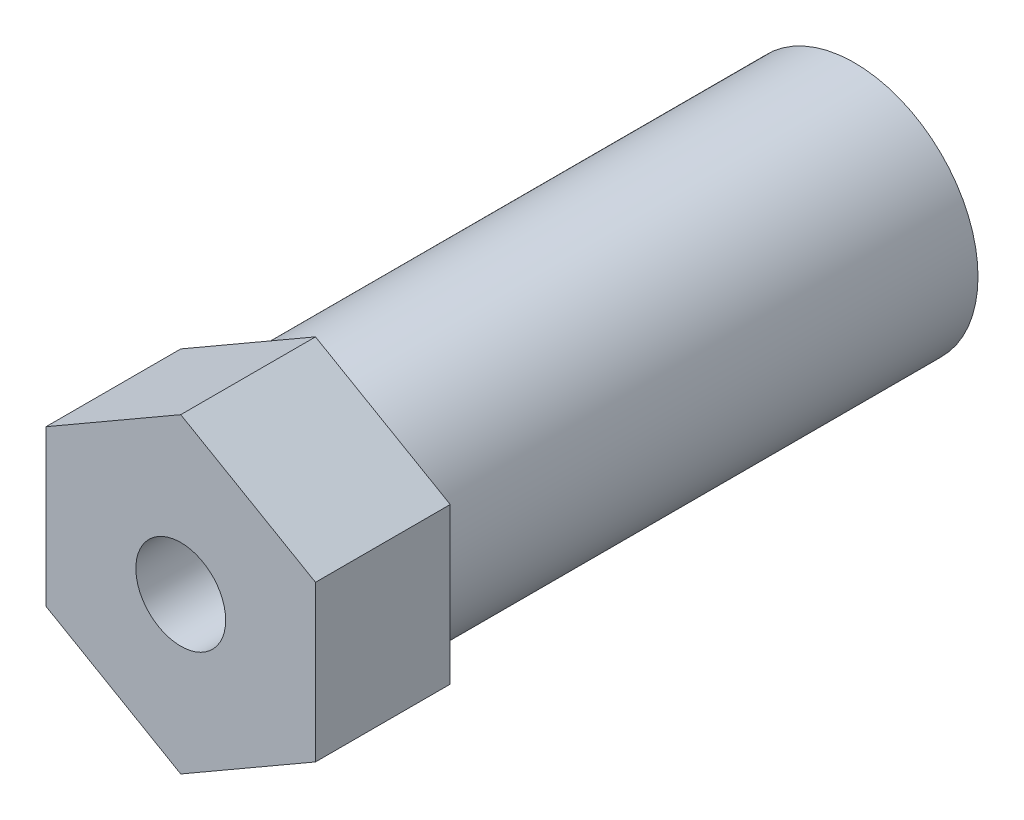
SolidWorks part; units mm, degrees
material "Brass"
ref_plane "Front Plane" through (0, 0, 0) normal (0, 0, 1) x (1, 0, 0)
ref_plane "Top Plane" through (0, 0, 0) normal (0, 1, 0) x (1, 0, 0)
ref_plane "Right Plane" through (0, 0, 0) normal (1, 0, 0) x (0, 0, -1)
sketch "Sketch1" plane through (0, 0, 0) normal (0, 0, 1) x (1, 0, 0)
  line L1 (6, 3.4641) -> (0, 6.9282)
  line L2 (0, 6.9282) -> (-6, 3.4641)
  line L3 (-6, 3.4641) -> (-6, -3.4641)
  line L4 (-6, -3.4641) -> (0, -6.9282)
  line L5 (0, -6.9282) -> (6, -3.4641)
  line L6 (6, -3.4641) -> (6, 3.4641)
  circle A0 centre (0, 0) radius 6 construction
  circle A1 centre (0, 0) radius 5.5
  circle A2 centre (0, 0) radius 2
  dimension "D2" = 11
  dimension "D3" = 4
  dimension "D1" = 12
extrude "Boss-Extrude1" add sketch "Sketch1" along normal blind 6 contours A1 | L5 L6 L1 L2 L3 L4 A1 region at (5.8167, 0, 0) region at (-5.3444, 0, 0)
extrude "Boss-Extrude3" add sketch "Sketch1<2>" against normal blind 24 separate body contours A1 region at (-5.3444, 0, 0)
sketch "Sketch1<2>" plane through (0, 0, 0) normal (0, 0, 1) x (1, 0, 0) same geometry as "Sketch1"
sketch "Sketch2" plane through (0, 0, -24) normal (0, 0, -1) x (-1, 0, 0)
  circle A0 centre (0, 0) radius 3
  point P3 (0, 0)
  dimension "D1" = 6
extrude "Cut-Extrude1" cut sketch "Sketch2" against normal blind 25
